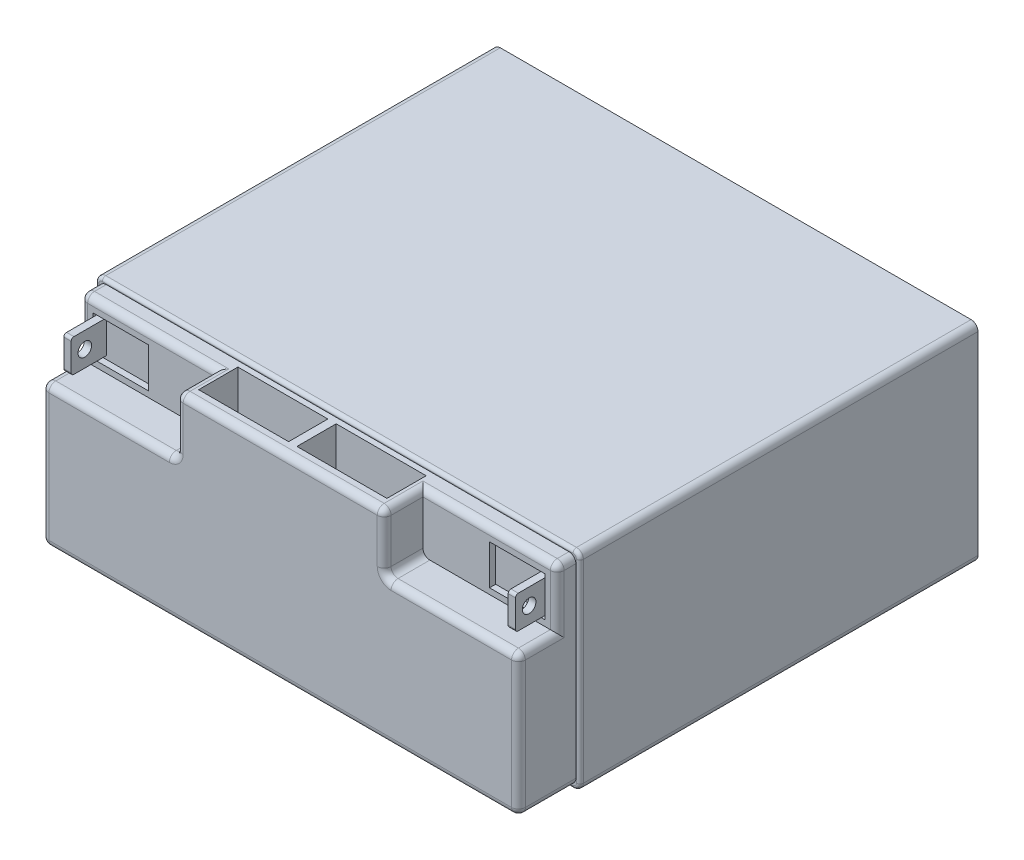
SolidWorks part; units mm, degrees
note: '?' marks a value the reader was unsure of.
ref_plane "Front Plane" through (0, 0, 0) normal (0, 0, 1) x (1, 0, 0)
ref_plane "Top Plane" through (0, 0, 0) normal (0, 1, 0) x (1, 0, 0)
ref_plane "Right Plane" through (0, 0, 0) normal (1, 0, 0) x (0, 0, -1)
ref_plane "Plane1" through (0, -62.2132, 0) normal (0, -1, 0) x (1, 0, 0)
sketch "Sketch1" plane through (0, -62.2132, 0) normal (0, -1, 0) x (1, 0, 0)
  line L0 (-33.1131, 0) -> (144.6869, 0)
  line L1 (144.6869, 0) -> (144.6869, 146.05)
  line L2 (144.6869, 146.05) -> (-33.1131, 146.05)
  line L3 (-33.1131, 146.05) -> (-33.1131, 0)
extrude "Boss-Extrude1" add sketch "Sketch1" against normal blind 76.2
sketch "Sketch2" plane through (0, 0, 146.05) normal (0, 0, 1) x (1, 0, 0)
  line L0 (143.2096, -60.7358) -> (-31.6357, -60.7358)
  line L1 (-31.6357, -60.7358) -> (-31.6357, 12.5094)
  line L2 (-31.6357, 12.5094) -> (143.2096, 12.5094)
  line L3 (143.2096, 12.5094) -> (143.2096, -60.7358)
extrude "Boss-Extrude2" add sketch "Sketch2" along normal blind 21.082
sketch "Sketch3" plane through (-31.6357, 0, 0) normal (-1, 0, 0) x (0, 0, 1)
  line L0 (152.908, 12.5094) -> (152.908, -8.8266)
  line L1 (152.908, -8.8266) -> (167.132, -8.8266)
  line L2 (167.132, -8.8266) -> (167.132, 12.5094)
  line L3 (167.132, 12.5094) -> (152.908, 12.5094)
extrude "Cut-Extrude1" cut sketch "Sketch3" against normal blind 49.276
sketch "Sketch4" plane through (0, 0, 152.908) normal (0, 0, 1) x (1, 0, 0)
  line L0 (-24.3791, -5.3674) -> (-27.0726, -5.3674)
  line L1 (-27.0726, -5.3674) -> (-27.0726, 6.6326)
  line L2 (-27.0726, 6.6326) -> (-24.3791, 6.6326)
  line L3 (-24.3791, 6.6326) -> (-24.3791, -5.3674)
extrude "Boss-Extrude3" add sketch "Sketch4" along normal blind 10.746
sketch "Sketch5" plane through (0, 0, 152.908) normal (0, 0, 1) x (1, 0, 0)
  line L0 (-27.0726, 6.6326) -> (-24.3791, 6.6326)
  line L1 (-24.3791, 6.6326) -> (-24.3791, -5.3674)
  line L2 (-24.3791, -5.3674) -> (-27.0726, -5.3674)
  line L3 (-27.0726, -5.3674) -> (-27.0726, -6.6776)
  line L4 (-27.0726, -6.6776) -> (-6.7872, -6.6776)
  line L5 (-6.7872, -6.6776) -> (-6.7872, 7.9428)
  line L6 (-6.7872, 7.9428) -> (-27.0726, 7.9428)
  line L7 (-27.0726, 7.9428) -> (-27.0726, 6.6326)
extrude "Cut-Extrude2" cut sketch "Sketch5" against normal blind 2.254
sketch "Sketch6" plane through (0, 12.5094, 0) normal (0, 1, 0) x (-1, 0, 0)
  line L0 (-143.2096, 152.908) -> (-93.9336, 152.908)
  line L1 (-93.9336, 152.908) -> (-93.9336, 167.132)
  line L2 (-93.9336, 167.132) -> (-143.2096, 167.132)
  line L3 (-143.2096, 167.132) -> (-143.2096, 152.908)
extrude "Cut-Extrude3" cut sketch "Sketch6" against normal blind 21.336
sketch "Sketch7" plane through (0, 0, 152.908) normal (0, 0, 1) x (1, 0, 0)
  line L0 (138.6465, -5.3674) -> (135.9529, -5.3674)
  line L1 (135.9529, -5.3674) -> (135.9529, 6.6326)
  line L2 (135.9529, 6.6326) -> (138.6465, 6.6326)
  line L3 (138.6465, 6.6326) -> (138.6465, -5.3674)
extrude "Boss-Extrude4" add sketch "Sketch7" along normal blind 10.746
sketch "Sketch8" plane through (0, 0, 152.908) normal (0, 0, 1) x (1, 0, 0)
  line L0 (138.6465, -5.3674) -> (135.9529, -5.3674)
  line L1 (135.9529, -5.3674) -> (135.9529, 6.6326)
  line L2 (135.9529, 6.6326) -> (138.6465, 6.6326)
  line L3 (138.6465, 6.6326) -> (138.6465, 7.9428)
  line L4 (138.6465, 7.9428) -> (118.361, 7.9428)
  line L5 (118.361, 7.9428) -> (118.361, -6.6776)
  line L6 (118.361, -6.6776) -> (138.6465, -6.6776)
  line L7 (138.6465, -6.6776) -> (138.6465, -5.3674)
extrude "Cut-Extrude4" cut sketch "Sketch8" against normal blind 2.254
sketch "Sketch9" plane through (0, 12.5094, 0) normal (0, 1, 0) x (-1, 0, 0)
  line L0 (-90.3309, 148.1138) -> (-57.3109, 148.1138)
  line L1 (-57.3109, 148.1138) -> (-57.3109, 162.5135)
  line L2 (-57.3109, 162.5135) -> (-90.3309, 162.5135)
  line L3 (-90.3309, 162.5135) -> (-90.3309, 148.1138)
extrude "Cut-Extrude5" cut sketch "Sketch9" against normal blind 19.05
sketch "Sketch10" plane through (0, 12.5094, 0) normal (0, 1, 0) x (-1, 0, 0)
  line L0 (-54.2629, 148.1138) -> (-21.2429, 148.1138)
  line L1 (-21.2429, 148.1138) -> (-21.2429, 162.5135)
  line L2 (-21.2429, 162.5135) -> (-54.2629, 162.5135)
  line L3 (-54.2629, 162.5135) -> (-54.2629, 148.1138)
extrude "Cut-Extrude6" cut sketch "Sketch10" against normal blind 19.05
sketch "Sketch11" plane through (0, -60.7358, 0) normal (0, -1, 0) x (1, 0, 0)
  line L0 (56.8496, 162.8434) -> (56.8496, 147.6421)
  line L1 (56.8496, 147.6421) -> (120.3496, 147.6421)
  line L2 (120.3496, 147.6421) -> (120.3496, 162.8434)
  line L3 (120.3496, 162.8434) -> (56.8496, 162.8434)
extrude "Cut-Extrude7" cut sketch "Sketch11" against normal blind 19.558
sketch "Sketch12" plane through (0, -60.7358, 0) normal (0, -1, 0) x (1, 0, 0)
  line L0 (-8.7757, 162.8434) -> (-8.7757, 147.6421)
  line L1 (-8.7757, 147.6421) -> (54.7243, 147.6421)
  line L2 (54.7243, 147.6421) -> (54.7243, 162.8434)
  line L3 (54.7243, 162.8434) -> (-8.7757, 162.8434)
extrude "Cut-Extrude8" cut sketch "Sketch12" against normal blind 19.558
hole_wizard "Ø5.0 (5) Diameter Hole1" positions "Sketch14" profile "Sketch13" hole size "Ø5.0" standard "Ansi Metric"
sketch "Sketch14" plane through (135.9529, 0, 0) normal (-1, 0, 0) x (0, 0, 1)
  point P0 (158.654, 0.6326)
sketch "Sketch13" plane through (135.9529, 0.6326, 158.654) normal (0, 1, 0) x (0, 0, 1)
  line L0 (0, 0) -> (0, 8.734)
  line L1 (0, 8.734) -> (2.5, 8.734)
  line L2 (2.5, 8.734) -> (2.5, 0)
  line L5 (2.5, 0) -> (0, 0)
  line L11 (0, -6.35) -> (0, 107.95) construction
  dimension "Thru Hole Dia." = 5
  dimension "Thru Hole Depth" = 8.734
hole_wizard "Ø5.0 (5) Diameter Hole2" positions "Sketch16" profile "Sketch15" hole size "Ø5.0" standard "Ansi Metric"
sketch "Sketch16" plane through (-24.3791, 0, 0) normal (1, 0, 0) x (0, 0, -1)
  point P0 (-158.654, 0.6326)
sketch "Sketch15" plane through (-24.3791, 0.6326, 158.654) normal (0, 1, 0) x (0, 0, -1)
  line L0 (0, 0) -> (0, 8.734)
  line L1 (0, 8.734) -> (2.5, 8.734)
  line L2 (2.5, 8.734) -> (2.5, 0)
  line L5 (2.5, 0) -> (0, 0)
  line L11 (0, -6.35) -> (0, 107.95) construction
  dimension "Thru Hole Dia." = 5
  dimension "Thru Hole Depth" = 8.734
fillet "Fillet1" radius 2.54 26 edges at (143.2096, -60.7358, 156.591) (143.2096, 1.8414, 152.908) (143.2096, 12.5094, 149.479) (-31.6357, -60.7358, 156.591) (55.7869, -60.7358, 167.132) (143.2096, -34.7812, 167.132) (143.2096, -8.8266, 160.02) (118.5716, 12.5094, 152.908) (-31.6357, 12.5094, 149.479) (-31.6357, 1.8414, 152.908) (-31.6357, -8.8266, 160.02) (-31.6357, -34.7812, 167.132) (93.9336, 1.8414, 167.132) (118.5716, -8.8266, 167.132) (93.9336, 12.5094, 160.02) (-6.9977, 12.5094, 152.908) (-6.9977, -8.8266, 167.132) (17.6403, 1.8414, 167.132) (55.7869, 12.5094, 167.132) (17.6403, 12.5094, 160.02) (17.6403, -8.8266, 160.02) (-33.1131, 13.9868, 73.025) (93.9336, -8.8266, 160.02) (144.6869, -62.2132, 73.025) (-33.1131, -62.2132, 73.025) (144.6869, 13.9868, 73.025) tangent propagation no
fillet "Fillet2" radius 1 4 edges at (-25.7258, -5.3674, 163.654) (-25.7258, 6.6326, 163.654) (137.2997, 6.6326, 163.654) (137.2997, -5.3674, 163.654) tangent propagation no
fillet "Fillet3" radius 1.27 8 edges at (-33.1131, -24.1132, 146.05) (-32.3691, 13.2428, 146.05) (-32.3691, -61.4693, 146.05) (55.7869, 13.9868, 146.05) (55.7869, -62.2132, 146.05) (143.943, 13.2428, 146.05) (143.943, -61.4693, 146.05) (144.6869, -24.1132, 146.05) tangent propagation no
ref_plane "Plane2" through (144.6869, 0, 0) normal (1, 0, 0) x (0, 0, -1)
sketch "0_0_Point" plane through (0, 0, 152.908) normal (0, 0, 1) x (1, 0, 0)
  line L0 (-27.0726, -5.3674) -> (-24.3791, 6.6326) construction
  point P0 (-25.7258, 0.6326)
other "0_0" parameters "Diameter"=2, "StubLength"=2
ref_axis "Axis1" through (-25.7258, 0.6326, 162.908) along (0, 0, -1)?
sketch "0_1_Point" plane through (0, 0, 152.908) normal (0, 0, 1) x (1, 0, 0)
  line L0 (135.9529, -5.3674) -> (138.6465, 6.6326) construction
  point P0 (137.2997, 0.6326)
other "0_1" parameters "Diameter"=2, "StubLength"=2
ref_axis "Axis2" through (137.2997, 0.6326, 162.908) along (0, 0, -1)?
